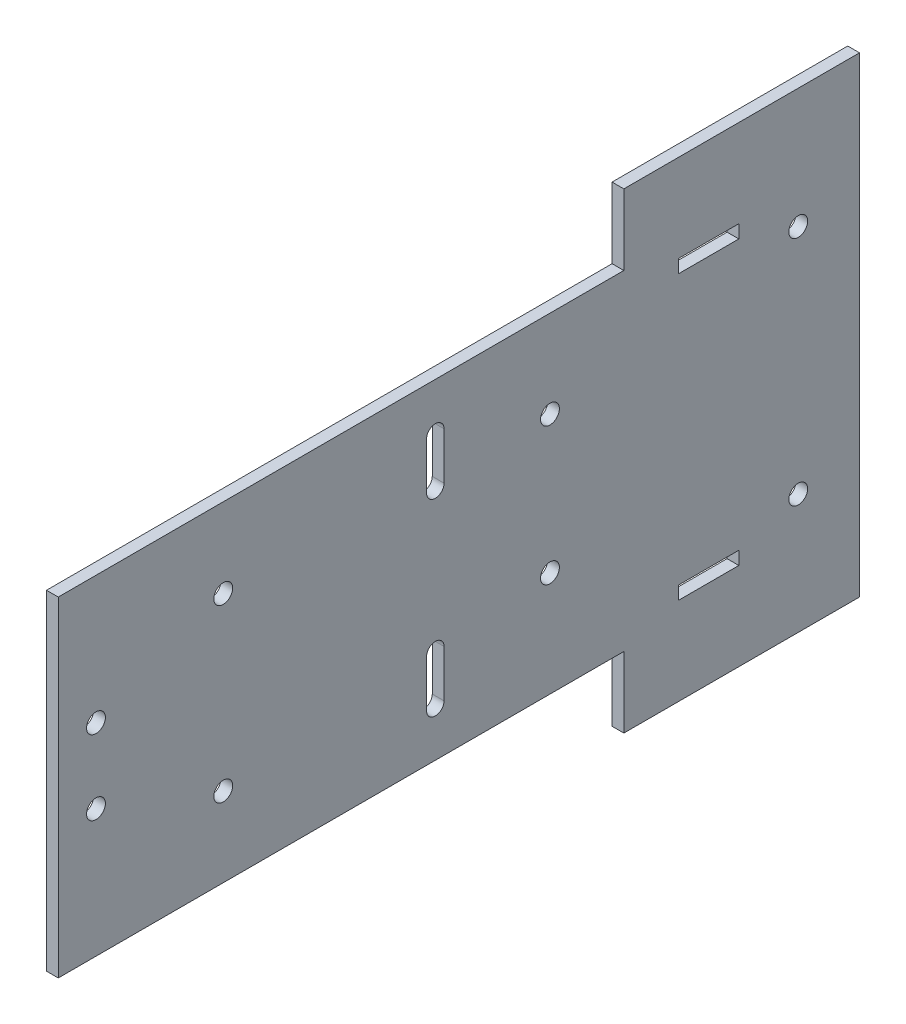
SolidWorks part; units mm, degrees
ref_plane "Front Plane" through (0, 0, 0) normal (1, 0, 0) x (0, 1, 0)
ref_plane "Top Plane" through (0, 0, 0) normal (0, 0, 1) x (0, 1, 0)
ref_plane "Right Plane" through (0, 0, 0) normal (0, 1, 0) x (-1, 0, 0)
sketch "Sketch1" plane through (0, 0, 0) normal (1, 0, 0) x (0, 1, 0)
  line L1 (50, 0) -> (50, 50)
  line L2 (50, 50) -> (35, 50)
  line L3 (35, 50) -> (35, 170)
  line L4 (35, 170) -> (-35, 170)
  line L5 (-35, 170) -> (-35, 50)
  line L6 (-35, 50) -> (-50, 50)
  line L7 (-50, 50) -> (-50, 0)
  line L8 (-50, 0) -> (0, 0)
  line L9 (0, 0) -> (50, 0)
  dimension "D1" = 50
  dimension "D2" = 50
  dimension "D3" = 70
  dimension "D4" = 120
extrude "Boss-Extrude1" add sketch "Sketch1" along normal blind 2.5 contours L5 L6 L7 L8 L9 L1 L2 L3 L4
sketch "Sketch4" plane through (0, 0, 0) normal (-1, 0, 0) x (0, -1, 0)
  line L0 (-28.6, 38.4) -> (-28.6, 25.6)
  line L1 (-28.6, 25.6) -> (-31.4, 25.6)
  line L2 (-31.4, 25.6) -> (-31.4, 38.4)
  line L3 (-31.4, 38.4) -> (-28.6, 38.4)
  line L4 (0, 0) -> (0, 170) construction
  line L5 (-35, 170) -> (35, 170) construction
  line L6 (-28.6, 32) -> (0, 32) construction
  line L7 (28.6, 38.4) -> (31.4, 38.4)
  line L8 (28.6, 38.4) -> (28.6, 25.6)
  line L9 (28.6, 25.6) -> (31.4, 25.6)
  line L10 (31.4, 38.4) -> (31.4, 25.6)
  line L11 (0, 32) -> (28.6, 32) construction
extrude "Cut-Extrude1" cut sketch "Sketch4" against normal through all
sketch "Sketch6" plane through (0, 0, 0) normal (-1, 0, 0) x (0, -1, 0)
  line L0 (-25, 91.85) -> (-15, 91.85)
  line L1 (15, 91.85) -> (25, 91.85)
  line L2 (25, 88.15) -> (15, 88.15)
  line L3 (-15, 88.15) -> (-25, 88.15)
  line L4 (-25, 90) -> (-35, 90) construction
  line L5 (-35, 50) -> (-35, 170) construction
  line L6 (25, 90) -> (35, 90) construction
  line L7 (35, 170) -> (35, 50) construction
  line L8 (-35, 170) -> (35, 170) construction
  arc A0 (-25, 88.15) -> (-25, 91.85) centre (-25, 90) cw
  arc A1 (-15, 91.85) -> (-15, 88.15) centre (-15, 90) cw
  arc A2 (15, 91.85) -> (15, 88.15) centre (15, 90) ccw
  arc A3 (25, 91.85) -> (25, 88.15) centre (25, 90) cw
  dimension "D1" = 3.7
  dimension "D2" = 10
  dimension "D3" = 30
  dimension "D4" = 80
extrude "Cut-Extrude2" cut sketch "Sketch6" against normal through all
sketch "Sketch7" plane through (2.5, 0, 0) normal (1, 0, 0) x (0, 1, 0)
  line L0 (-18.15, 135) -> (-35, 135) construction
  line L1 (-35, 170) -> (-35, 50) construction
  line L2 (18.15, 135) -> (35, 135) construction
  line L3 (35, 50) -> (35, 170) construction
  line L4 (35, 170) -> (-35, 170) construction
  circle A0 centre (-18.15, 135) radius 2
  circle A1 centre (18.15, 135) radius 2
  point P4 (0, 0)
  dimension "D1" = 4
  dimension "D2" = 35
  dimension "D3" = 36.3
extrude "Cut-Extrude3" cut sketch "Sketch7" against normal through all
sketch "Sketch8" plane through (0, 0, 0) normal (-1, 0, 0) x (0, -1, 0)
  line L0 (-35, 170) -> (35, 170) construction
  line L1 (-7.9, 162) -> (-35, 162) construction
  line L2 (-35, 50) -> (-35, 170) construction
  line L3 (7.9, 162) -> (35, 162) construction
  line L4 (35, 170) -> (35, 50) construction
  circle A0 centre (-7.9, 162) radius 2
  circle A1 centre (7.9, 162) radius 2
  dimension "D1" = 4
  dimension "D2" = 8
  dimension "D3" = 15.8
extrude "Cut-Extrude4" cut sketch "Sketch8" against normal through all
sketch "Sketch9" plane through (2.5, 0, 0) normal (1, 0, 0) x (0, 1, 0)
  line L0 (-50, 0) -> (50, 0) construction
  line L1 (-24.585, 13) -> (-50, 13) construction
  line L2 (-50, 50) -> (-50, 0) construction
  line L3 (24.585, 13) -> (50, 13) construction
  line L4 (50, 0) -> (50, 50) construction
  circle A0 centre (-24.585, 13) radius 2
  circle A1 centre (24.585, 13) radius 2
  circle A2 centre (16.4568, 65.6766) radius 2
  circle A3 centre (-12.7032, 65.6766) radius 2
  dimension "D1" = 4
  dimension "D2" = 13
  dimension "D3" = 49.17
  dimension "D4" = 29.16
  dimension "D5" = 54
  dimension "D6" = 53.3
extrude "Cut-Extrude5" cut sketch "Sketch9" against normal through all
